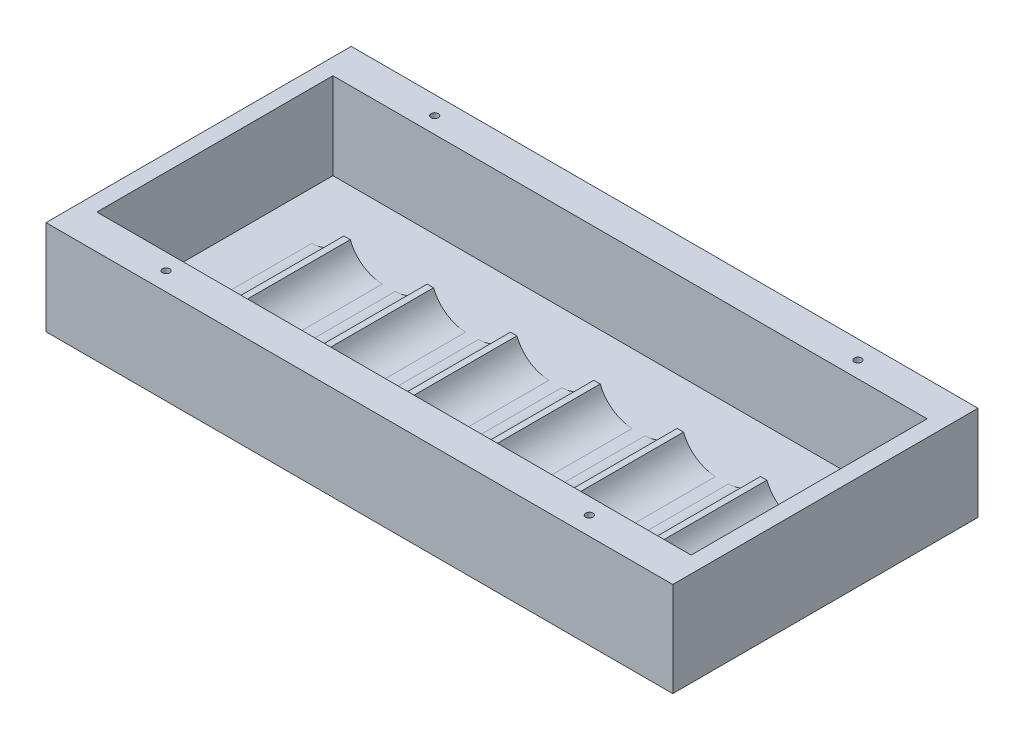
SolidWorks part; units mm, degrees
material "ABS"
ref_plane "Front Plane" through (0, 0, 0) normal (0, 0, 1) x (1, 0, 0)
ref_plane "Top Plane" through (0, 0, 0) normal (0, 1, 0) x (1, 0, 0)
ref_plane "Right Plane" through (0, 0, 0) normal (1, 0, 0) x (0, 0, -1)
sketch "Sketch1" plane through (0, 0, 0) normal (0, 1, 0) x (1, 0, 0)
  line L0 (5.08, -5.08) -> (5.08, -78.74)
  line L1 (0, 0) -> (195.58, 0)
  line L2 (0, 0) -> (0, -83.82)
  line L3 (0, -83.82) -> (195.58, -83.82)
  line L4 (195.58, 0) -> (195.58, -83.82)
  line L5 (5.08, -78.74) -> (190.5, -78.74)
  line L6 (190.5, -5.08) -> (190.5, -78.74)
  line L7 (5.08, -5.08) -> (190.5, -5.08)
  line L8 (0, 0) -> (0, 5.715)
  line L9 (0, 5.715) -> (195.58, 5.715)
  line L10 (195.58, 5.715) -> (195.58, 0)
  line L11 (0, -83.82) -> (0, -89.535)
  line L12 (0, -89.535) -> (195.58, -89.535)
  line L13 (195.58, -89.535) -> (195.58, -83.82)
  dimension "D1" = 73.66
  dimension "D2" = 185.42
  dimension "D4" = 10.795
  dimension "D5" = 95.25
  dimension "D3" = 5.08
extrude "Boss-Extrude1" add sketch "Sketch1" against normal blind 2.5 contours L2 L3 L4 L1
extrude "Boss-Extrude2" add sketch "Sketch1<3>" along normal blind 27 contours L10 L9 L8 L1 | L12 L13 L3 L11 | L4 L1 L2 L3 L0 L7 L6 L5 region at (97.79, 0, -2.8575) region at (97.79, 0, 2.1278) region at (97.79, 0, 86.6775)
sketch "Sketch1<3>" plane through (0, 0, 0) normal (0, 1, 0) x (1, 0, 0) same geometry as "Sketch1"
sketch "Sketch2" plane through (0, 0, 0) normal (0, 1, 0) x (-1, 0, 0)
  line L0 (-31.08, 0) -> (-31.08, 83.82) construction
  line L1 (-5.08, 5.08) -> (-5.08, 78.74) construction
  line L2 (-20.08, 0) -> (-20.08, 83.82) construction
  line L9 (0, 0) -> (-195.58, 0) construction
  line L10 (0, 83.82) -> (-195.58, 83.82) construction
  dimension "D1" = 26
  dimension "D2" = 15
sketch "Sketch5" plane through (0, 0, 5.08) normal (0, 0, 1) x (1, 0, 0)
  line L0 (31.08, 0) -> (31.08, 7) construction
  line L1 (32.08, 7) -> (30.08, 7)
  line L2 (0, 0) -> (195.58, 0) construction
  line L3 (20.08, 0) -> (42.08, 0)
  line L16 (58.08, 7) -> (56.08, 7)
  line L17 (46.08, 0) -> (68.08, 0)
  line L18 (57.08, 0) -> (57.08, 7) construction
  line L19 (84.08, 7) -> (82.08, 7)
  line L20 (72.08, 0) -> (94.08, 0)
  line L21 (83.08, 0) -> (83.08, 7) construction
  line L22 (110.08, 7) -> (108.08, 7)
  line L23 (98.08, 0) -> (120.08, 0)
  line L24 (109.08, 0) -> (109.08, 7) construction
  line L25 (136.08, 7) -> (134.08, 7)
  line L26 (124.08, 0) -> (146.08, 0)
  line L27 (135.08, 0) -> (135.08, 7) construction
  line L28 (162.08, 7) -> (160.08, 7)
  line L29 (150.08, 0) -> (172.08, 0)
  line L30 (161.08, 0) -> (161.08, 7) construction
  line L37 (172.6, 7) -> (170.6, 7) [skipped]
  line L38 (160.6, 0) -> (182.6, 0) [skipped]
  line L39 (171.6, 0) -> (171.6, 7) construction
  line L40 (148.18, 0) -> (148.18, 7) construction
  line L41 (137.18, 0) -> (159.18, 0) [skipped]
  line L42 (149.18, 7) -> (147.18, 7) [skipped]
  line L43 (124.76, 0) -> (124.76, 7) construction
  line L44 (113.76, 0) -> (135.76, 0) [skipped]
  line L45 (125.76, 7) -> (123.76, 7) [skipped]
  line L46 (101.34, 0) -> (101.34, 7) construction
  line L47 (90.34, 0) -> (112.34, 0) [skipped]
  line L48 (102.34, 7) -> (100.34, 7) [skipped]
  line L49 (77.92, 0) -> (77.92, 7) construction
  line L50 (66.92, 0) -> (88.92, 0) [skipped]
  line L51 (78.92, 7) -> (76.92, 7) [skipped]
  line L52 (54.5, 0) -> (54.5, 7) construction
  line L53 (43.5, 0) -> (65.5, 0) [skipped]
  line L54 (55.5, 7) -> (53.5, 7) [skipped]
  arc A0 (20.08, 0) -> (30.08, 7) centre (19.832, 10.9972) ccw
  arc A1 (42.08, 0) -> (32.08, 7) centre (42.328, 10.9972) cw
  arc A10 (68.08, 0) -> (58.08, 7) centre (68.328, 10.9972) cw
  arc A11 (46.08, 0) -> (56.08, 7) centre (45.832, 10.9972) ccw
  arc A12 (94.08, 0) -> (84.08, 7) centre (94.328, 10.9972) cw
  arc A13 (72.08, 0) -> (82.08, 7) centre (71.832, 10.9972) ccw
  arc A14 (120.08, 0) -> (110.08, 7) centre (120.328, 10.9972) cw
  arc A15 (98.08, 0) -> (108.08, 7) centre (97.832, 10.9972) ccw
  arc A16 (146.08, 0) -> (136.08, 7) centre (146.328, 10.9972) cw
  arc A17 (124.08, 0) -> (134.08, 7) centre (123.832, 10.9972) ccw
  arc A18 (172.08, 0) -> (162.08, 7) centre (172.328, 10.9972) cw
  arc A19 (150.08, 0) -> (160.08, 7) centre (149.832, 10.9972) ccw
  arc A24 (182.6, 0) -> (172.6, 7) centre (182.848, 10.9972) cw [skipped]
  arc A25 (160.6, 0) -> (170.6, 7) centre (160.352, 10.9972) ccw [skipped]
  arc A26 (137.18, 0) -> (147.18, 7) centre (136.932, 10.9972) ccw [skipped]
  arc A27 (159.18, 0) -> (149.18, 7) centre (159.428, 10.9972) cw [skipped]
  arc A28 (113.76, 0) -> (123.76, 7) centre (113.512, 10.9972) ccw [skipped]
  arc A29 (135.76, 0) -> (125.76, 7) centre (136.008, 10.9972) cw [skipped]
  arc A30 (90.34, 0) -> (100.34, 7) centre (90.092, 10.9972) ccw [skipped]
  arc A31 (112.34, 0) -> (102.34, 7) centre (112.588, 10.9972) cw [skipped]
  arc A32 (66.92, 0) -> (76.92, 7) centre (66.672, 10.9972) ccw [skipped]
  arc A33 (88.92, 0) -> (78.92, 7) centre (89.168, 10.9972) cw [skipped]
  arc A34 (65.5, 0) -> (55.5, 7) centre (65.748, 10.9972) cw [skipped]
  arc A35 (43.5, 0) -> (53.5, 7) centre (43.252, 10.9972) ccw [skipped]
  dimension "D2" = 11
  dimension "D1" = 1
  dimension "D3" = 7
  dimension "D4" = 6
  dimension "D5" = 6
extrude "Boss-Extrude3" add sketch "Sketch5" along normal blind 32.5 from offset 21.59
extrude "Boss-Extrude4" add sketch "Sketch1<4>" against normal up to surface (2.5 mm away) contours L10 L9 L8 L1 | L12 L13 L3 L11 region at (97.79, 0, -2.8575) region at (97.79, 0, 86.6775) up to face at (97.79, -2.5, 41.91)
sketch "Sketch1<4>" plane through (0, 0, 0) normal (0, 1, 0) x (1, 0, 0) same geometry as "Sketch1"
sketch "Sketch6" plane through (0, 27, 0) normal (0, 1, 0) x (1, 0, 0)
  line L0 (0, 0) -> (195.58, 0) construction
  line L1 (195.58, 5.715) -> (195.58, -89.535) construction
  line L2 (0, -89.535) -> (0, 5.715) construction
  line L3 (0, -41.91) -> (14.6137, -41.91) construction
  point P5 (31.75, 0)
  point P6 (163.83, 0)
  point P9 (163.83, -83.82)
  point P10 (31.75, -83.82)
  dimension "D1" = 31.75
  dimension "D2" = 31.75
hole_wizard "#4-40 Tapped Hole2" positions "Sketch10" profile "Sketch9" tap size "#4-40" standard "Ansi Inch"
sketch "Sketch10" plane through (0, 27, 0) normal (0, 1, 0) x (-1, 0, 0)
  point P0 (-31.75, 0)
  point P1 (-163.83, 0)
  point P8 (-31.75, 83.82)
  point P11 (-163.83, 83.82)
sketch "Sketch9" plane through (31.75, 27, 0) normal (1, 0, 0) x (0, 0, 1)
  line L0 (0, 0) -> (0, 8.2992)
  line L1 (0, 8.2992) -> (1.1303, 7.62)
  line L2 (1.1303, 7.62) -> (1.1303, 0)
  line L5 (1.1303, 0) -> (0, 0)
  line L10 (0, 8.2992) -> (-1.1303, 7.62) construction
  line L11 (0, -6.35) -> (0, 107.95) construction
  dimension "Tap Drill Dia." = 2.2606
  dimension "Tap Drill Depth" = 7.62
  dimension "Drill Angle" = 118
cosmetic thread "Hole Thread2" parameters "D1"=5.588, "D2"=2.8448
cosmetic thread "Hole Thread3" parameters "D1"=5.588, "D2"=2.8448
cosmetic thread "Hole Thread4" parameters "D1"=5.588, "D2"=2.8448
cosmetic thread "Hole Thread5" parameters "D1"=5.588, "D2"=2.8448
sketch "midpoint" plane through (0, 27, 0) normal (0, 1, 0) x (1, 0, 0)
  line L0 (97.79, 5.715) -> (97.79, -89.535) construction
  line L1 (0, 5.715) -> (195.58, 5.715) construction
  line L2 (0, -89.535) -> (195.58, -89.535) construction
